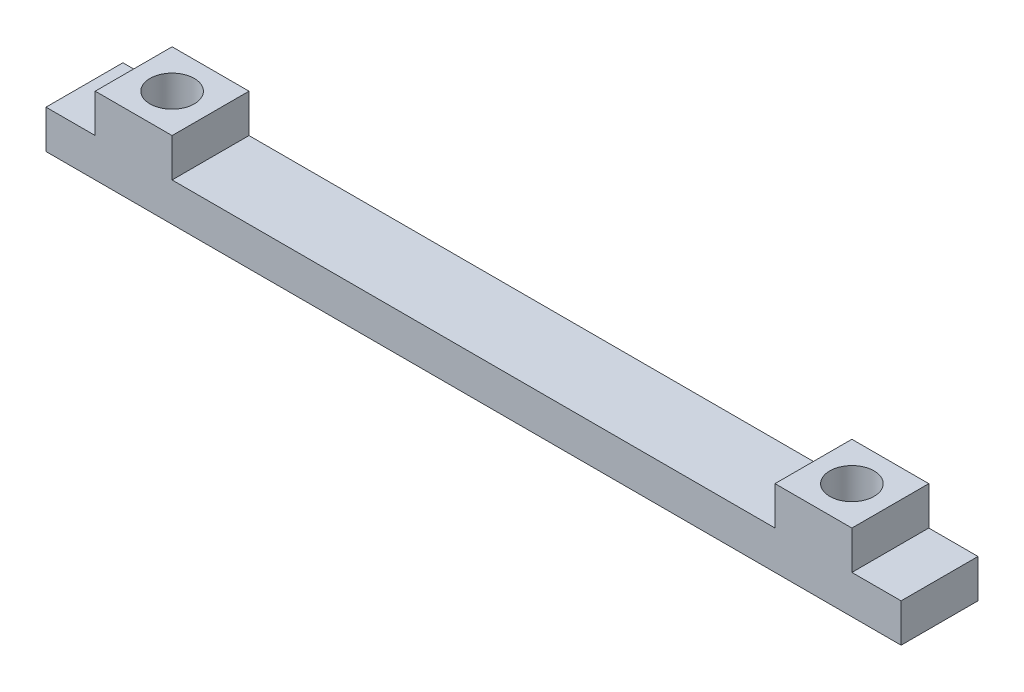
SolidWorks part; units mm, degrees
material "Alloy Steel"
ref_plane "Front Plane" through (0, 0, 0) normal (0, 0, 1) x (1, 0, 0)
ref_plane "Top Plane" through (0, 0, 0) normal (0, 1, 0) x (1, 0, 0)
ref_plane "Right Plane" through (0, 0, 0) normal (1, 0, 0) x (0, 0, -1)
sketch "Sketch1" plane through (0, 0, 0) normal (0, 0, 1) x (1, 0, 0)
  line L0 (35.306, 0) -> (35.306, 3.175) construction
  line L1 (0, 0) -> (70.612, 0)
  line L2 (0, 0) -> (0, 3.175)
  line L3 (0, 3.175) -> (70.612, 3.175)
  line L4 (70.612, 0) -> (70.612, 3.175)
  line L5 (4.064, 3.175) -> (10.414, 3.175)
  line L6 (4.064, 3.175) -> (4.064, 6.35)
  line L7 (4.064, 6.35) -> (10.414, 6.35)
  line L8 (10.414, 3.175) -> (10.414, 6.35)
  line L9 (60.198, 3.175) -> (66.548, 3.175)
  line L10 (60.198, 3.175) -> (60.198, 6.35)
  line L11 (60.198, 6.35) -> (66.548, 6.35)
  line L12 (66.548, 3.175) -> (66.548, 6.35)
  dimension "D1" = 4.064
  dimension "D2" = 3.175
  dimension "D4" = 49.784
  dimension "D5" = 3.175
  dimension "D6" = 6.35
extrude "Boss-Extrude1" add sketch "Sketch1" along normal blind 6.35 contours L1 L0 L3 L2 | L3 L8 L7 L6 | L3 L12 L11 L10 | L0 L1 L4 L3 region at (17.653, 1.5875, 0) region at (52.959, 1.5875, 0) region at (7.239, 4.7625, 0) region at (63.373, 4.7625, 0)
sketch "Sketch2" plane through (0, 0, 0) normal (0, -1, 0) x (1, 0, 0)
  line L0 (70.612, 3.175) -> (0, 3.175) construction
  line L1 (70.612, 6.35) -> (70.612, 0) construction
  line L2 (0, 6.35) -> (0, 0) construction
  line L3 (7.239, 6.35) -> (7.239, 0) construction
  line L4 (63.373, 6.35) -> (63.373, 0) construction
  line L7 (4.064, 0) -> (10.414, 0)
  line L8 (4.064, 6.35) -> (4.064, 0)
  line L9 (10.414, 6.35) -> (4.064, 6.35)
  line L10 (10.414, 0) -> (10.414, 6.35)
  line L11 (4.064, 0) -> (10.414, 0)
  line L12 (4.064, 6.35) -> (4.064, 0)
  line L13 (10.414, 6.35) -> (4.064, 6.35)
  line L14 (10.414, 0) -> (10.414, 6.35)
  line L15 (60.198, 0) -> (66.548, 0)
  line L16 (60.198, 6.35) -> (60.198, 0)
  line L17 (66.548, 6.35) -> (60.198, 6.35)
  line L18 (66.548, 0) -> (66.548, 6.35)
  line L19 (60.198, 0) -> (66.548, 0)
  line L20 (60.198, 6.35) -> (60.198, 0)
  line L21 (66.548, 6.35) -> (60.198, 6.35)
  line L22 (66.548, 0) -> (66.548, 6.35)
  point P18 (7.239, 3.175)
  point P19 (63.373, 3.175)
  dimension "D1" = 0
  dimension "D2" = 0
hole_wizard "#6 Clearance Hole1" positions "3DSketch1" profile "Sketch4" hole size "#6" standard "ANSI Inch" end condition through all
sketch3d "3DSketch1"
  point P0 (7.239, 0, 3.175)
  point P4 (63.373, 0, 3.175)
sketch "Sketch4" plane through (7.239, 0, 3.175) normal (1, 0, 0) x (0, 0, -1)
  line L0 (0, 0) -> (0, 6.35)
  line L1 (0, 6.35) -> (1.8288, 6.35)
  line L2 (1.8288, 6.35) -> (1.8288, 0)
  line L5 (1.8288, 0) -> (0, 0)
  line L11 (0, -6.35) -> (0, 107.95) construction
  dimension "Thru Hole Dia." = 3.6576
  dimension "Thru Hole Depth" = 6.35
scale "Scale1" [suppressed]
